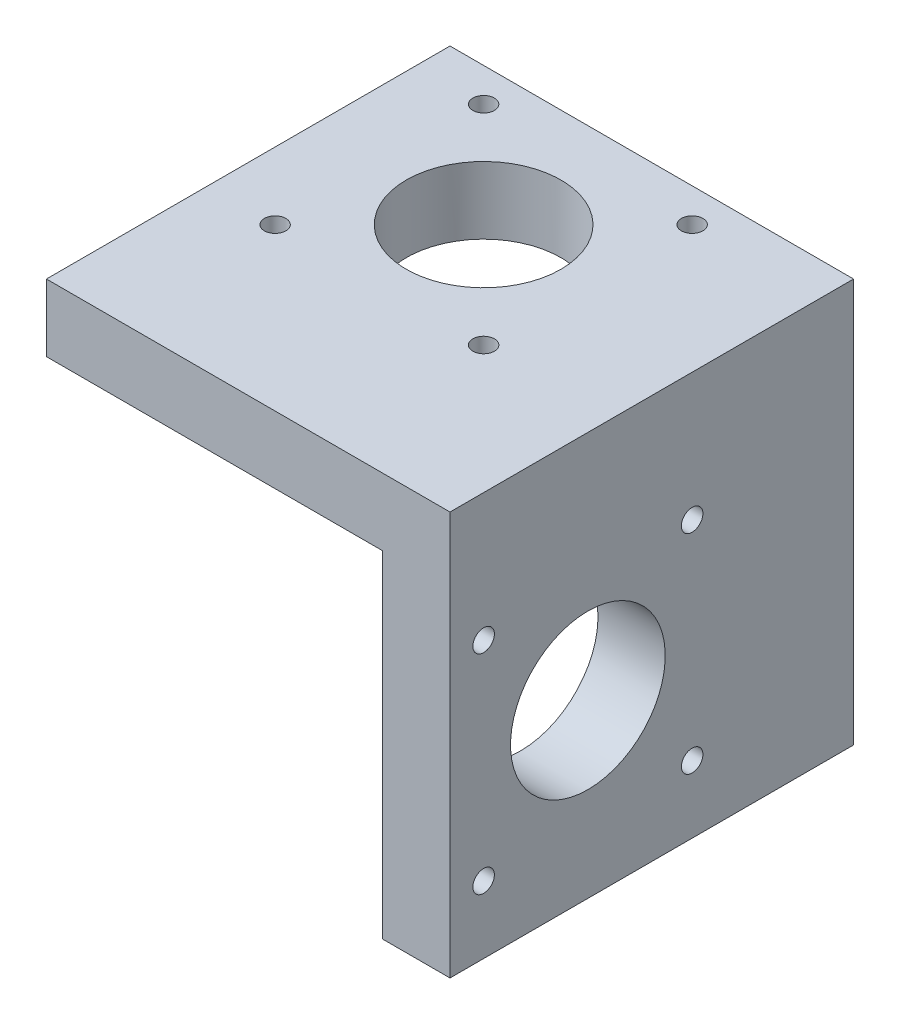
SolidWorks part; units mm, degrees
ref_plane "前视基准面" through (0, 0, 0) normal (0, 0, 1) x (1, 0, 0)
ref_plane "上视基准面" through (0, 0, 0) normal (0, 1, 0) x (1, 0, 0)
ref_plane "右视基准面" through (0, 0, 0) normal (1, 0, 0) x (0, 0, -1)
sketch "草图1" plane through (0, 0, 0) normal (0, 0, 1) x (1, 0, 0)
  line L1 (-47.5, 20.0735) -> (12.5, 20.0735)
  line L2 (-47.5, 20.0735) -> (-47.5, 10.0735)
  line L3 (-47.5, 10.0735) -> (2.5, 10.0735)
  line L4 (12.5, 20.0735) -> (12.5, 10.0735)
  line L5 (12.5, 20.0735) -> (2.5, 20.0735)
  line L6 (12.5, 20.0735) -> (12.5, -39.9265)
  line L7 (12.5, -39.9265) -> (2.5, -39.9265)
  line L8 (2.5, 10.0735) -> (2.5, -39.9265)
  dimension "D1" = 10
  dimension "D2" = 10
  dimension "D3" = 60
  dimension "D4" = 60
extrude "凸台-拉伸1" add sketch "草图1" along normal blind 60 contours L3 L8 L7 L6 L4 L1 L2 region at (-22.5, 19.225, 0)
sketch "草图2" plane through (0, 10.0735, 0) normal (0, -1, 0) x (1, 0, 0)
  line L0 (-47.5, 0) -> (2.5, 0) construction
  line L1 (-37.5, 36) -> (-6.5, 36) construction
  line L2 (-37.5, 36) -> (-37.5, 5) construction
  line L3 (-37.5, 5) -> (-6.5, 5) construction
  line L4 (-6.5, 36) -> (-6.5, 5) construction
  line L5 (-47.5, 60) -> (-47.5, 0) construction
  line L6 (-37.5, 36) -> (-6.5, 5) construction
  circle A0 centre (-37.5, 36) radius 1.6
  circle A1 centre (-37.5, 5) radius 1.6
  circle A2 centre (-6.5, 5) radius 1.6
  circle A3 centre (-6.5, 36) radius 1.6
  circle A4 centre (-22, 20.5) radius 11.5
  dimension "D3" = 3.2
  dimension "D6" = 23
  dimension "D1" = 31
  dimension "D2" = 31
  dimension "D4" = 5
  dimension "D5" = 10
extrude "切除-拉伸1" cut sketch "草图2" against normal blind 60
sketch "草图4" plane through (2.5, 0, 0) normal (-1, 0, 0) x (0, 0, 1)
  line L0 (60, 10.0735) -> (60, -39.9265) construction
  line L1 (24, 1.0735) -> (55, 1.0735) construction
  line L2 (24, 1.0735) -> (24, -29.9265) construction
  line L3 (24, -29.9265) -> (55, -29.9265) construction
  line L4 (55, 1.0735) -> (55, -29.9265) construction
  line L5 (60, -39.9265) -> (0, -39.9265) construction
  line L6 (24, 1.0735) -> (55, -29.9265) construction
  circle A0 centre (24, 1.0735) radius 1.6
  circle A1 centre (24, -29.9265) radius 1.6
  circle A2 centre (55, -29.9265) radius 1.6
  circle A3 centre (55, 1.0735) radius 1.6
  circle A4 centre (39.5, -14.4265) radius 11.5
  dimension "D3" = 3.2
  dimension "D6" = 23
  dimension "D1" = 31
  dimension "D2" = 31
  dimension "D4" = 5
  dimension "D5" = 10
extrude "切除-拉伸2" cut sketch "草图4" against normal blind 60
